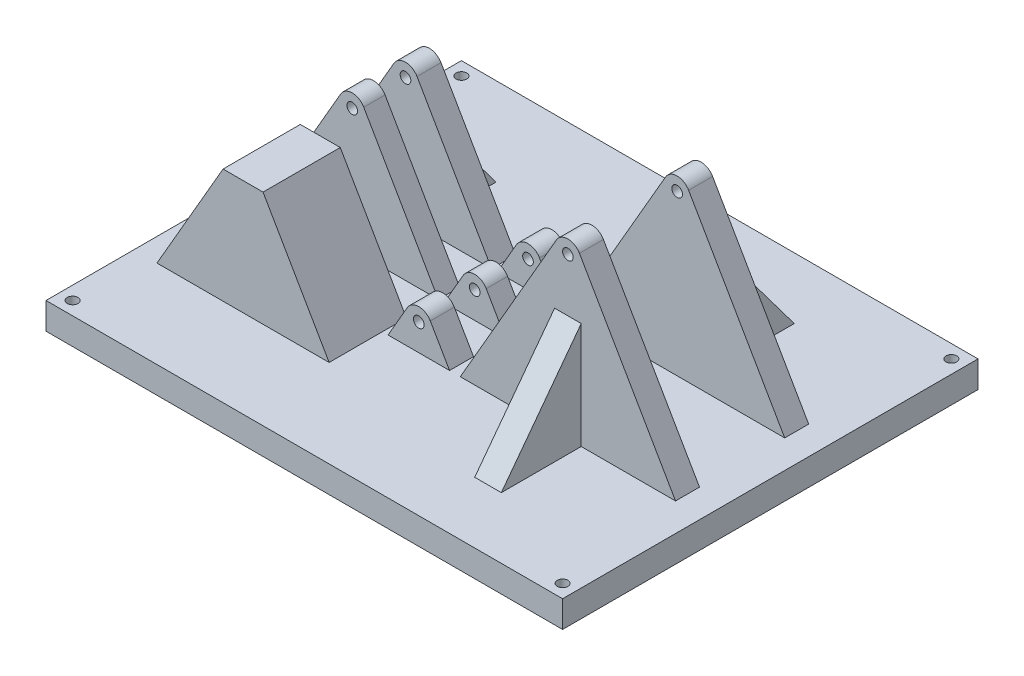
SolidWorks part; units mm, degrees
ref_plane "Front Plane" through (0, 0, 0) normal (0, 0, 1) x (1, 0, 0)
ref_plane "Top Plane" through (0, 0, 0) normal (0, 1, 0) x (1, 0, 0)
ref_plane "Right Plane" through (0, 0, 0) normal (1, 0, 0) x (0, 0, -1)
sketch "Sketch2" plane through (0, 0, 0) normal (0, 0, 1) x (1, 0, 0)
  line L0 (41.6699, 12.5) -> (5.5855, -50)
  line L1 (-97, -50) -> (97, -50)
  line L2 (-97, -50) -> (-97, 50)
  line L3 (-97, 50) -> (97, 50)
  line L4 (97, -50) -> (97, 50)
  line L5 (-97, -50) -> (97, 50) construction
  line L6 (-97, 50) -> (97, -50) construction
  line L7 (-88.3316, -50) -> (-60.3301, -1.5)
  line L8 (-23.6684, -50) -> (-51.6699, -1.5)
  line L9 (-14.3301, -37.5) -> (-21.547, -50)
  line L10 (-5.6699, -37.5) -> (1.547, -50)
  line L11 (50.3301, 12.5) -> (86.4145, -50)
  circle A0 centre (-10, -40) radius 2
  circle A1 centre (-56, -4) radius 2
  circle A2 centre (46, 10) radius 2
  arc A3 (-51.6699, -1.5) -> (-60.3301, -1.5) centre (-56, -4) ccw
  arc A5 (-5.6699, -37.5) -> (-14.3301, -37.5) centre (-10, -40) ccw
  arc A6 (50.3301, 12.5) -> (41.6699, 12.5) centre (46, 10) ccw
  point P0 (0, 0)
extrude "Boss-Extrude2" add sketch "Sketch2" along normal mid plane 10 contours L11 A6 L0 L1 A2 | L10 A5 L9 L1 A0 | L8 A3 L7 L1 A1 region at (46, -27.0942, 0) region at (-10, -44.3629, 0) region at (-56, -31.8498, 0)
sketch "Sketch3" plane through (0, -50, 0) normal (0, -1, 0) x (-1, 0, 0)
  line L1 (97, 78) -> (-97, 78)
  line L2 (97, 78) -> (97, -78)
  line L3 (97, -78) -> (-97, -78)
  line L4 (-97, 78) -> (-97, -78)
  line L5 (97, 78) -> (-97, -78) construction
  line L6 (97, -78) -> (-97, 78) construction
  point P0 (0, 0)
extrude "Boss-Extrude3" add sketch "Sketch3" along normal blind 10
ref_plane "Plane1" through (0, 0, 15) normal (0, 0, 1) x (1, 0, 0)
sketch "Sketch5" plane through (0, 0, 15) normal (0, 0, 1) x (1, 0, 0)
  line L0 (41.6699, 12.5) -> (5.5855, -50)
  line L1 (-97, -50) -> (97, -50)
  line L2 (-97, -50) -> (-97, 50)
  line L3 (-97, 50) -> (97, 50)
  line L4 (97, -50) -> (97, 50)
  line L5 (-97, -50) -> (97, 50) construction
  line L6 (-97, 50) -> (97, -50) construction
  line L7 (-88.3316, -50) -> (-60.3301, -1.5)
  line L8 (-23.6684, -50) -> (-51.6699, -1.5)
  line L9 (-14.3301, -37.5) -> (-21.547, -50)
  line L10 (-5.6699, -37.5) -> (1.547, -50)
  line L11 (50.3301, 12.5) -> (86.4145, -50)
  circle A0 centre (-10, -40) radius 2
  circle A1 centre (-56, -4) radius 2
  circle A2 centre (46, 10) radius 2
  arc A3 (-51.6699, -1.5) -> (-60.3301, -1.5) centre (-56, -4) ccw
  arc A4 (-5.6699, -37.5) -> (-14.3301, -37.5) centre (-10, -40) ccw
  arc A5 (50.3301, 12.5) -> (41.6699, 12.5) centre (46, 10) ccw
  point P0 (0, 0)
extrude "Boss-Extrude4" add sketch "Sketch5" along normal blind 10 contours L8 A3 L7 L1 A1 | L10 A4 L9 L1 A0 | L11 A5 L0 L1 A2 region at (46, -27.0942, 15) region at (-10, -44.3629, 15) region at (-56, -31.8498, 15)
mirror "Mirror1" about plane through (0, 0, 0) normal (0, 0, 1) of "Boss-Extrude4"
sketch "Sketch6" plane through (0, -50, 0) normal (0, 1, 0) x (1, 0, 0)
  line L1 (5.5855, 5) -> (86.4145, 5)
  line L2 (5.5855, 5) -> (5.5855, -5)
  line L3 (5.5855, -5) -> (86.4145, -5)
  line L4 (86.4145, 5) -> (86.4145, -5)
extrude "Cut-Extrude1" cut sketch "Sketch6" along normal blind 142
sketch "Sketch7" plane through (0, -50, 0) normal (0, 1, 0) x (1, 0, 0)
  line L5 (-97, -78) -> (97, 78) construction
  line L6 (-97, 78) -> (97, -78) construction
  circle A5 centre (-92, -73) radius 2
  circle A6 centre (-92, 73) radius 2
  circle A7 centre (92, 73) radius 2
  circle A8 centre (92, -73) radius 2
  point P0 (0, 0)
extrude "Cut-Extrude2" cut sketch "Sketch7" against normal blind 142
sketch "Sketch8" plane through (0, 0, 25) normal (0, 0, 1) x (1, 0, 0)
  line L2 (-71, -7) -> (-41, -7)
  line L3 (-71, -7) -> (-71, -1)
  line L5 (-41, -7) -> (-41, -1)
  line L9 (-71, -1) -> (-71, 3.0286)
  line L10 (-71, 3.0286) -> (-41, 3.0286)
  line L11 (-41, -1) -> (-41, 3.0286)
extrude "Cut-Extrude4" cut sketch "Sketch8" against normal blind 10
sketch "Sketch9" plane through (0, 0, 25) normal (0, 0, 1) x (1, 0, 0)
  line L0 (-88.3316, -50) -> (-23.6684, -50)
  line L1 (-23.6684, -50) -> (-48.4944, -7)
  line L2 (-48.4944, -7) -> (-63.5056, -7)
  line L3 (-63.5056, -7) -> (-88.3316, -50)
extrude "Boss-Extrude5" add sketch "Sketch9" along normal blind 20
sketch "Sketch10" plane through (0, 0, 5) normal (0, 0, 1) x (1, 0, 0)
  line L0 (-60.3301, -1.5) -> (-88.3316, -50)
  line L1 (-88.3316, -50) -> (-23.6684, -50)
  line L2 (-23.6684, -50) -> (-51.6699, -1.5)
  line L3 (-21.547, -50) -> (-14.3301, -37.5)
  line L5 (-5.6699, -37.5) -> (1.547, -50)
  line L6 (1.547, -50) -> (-21.547, -50)
  arc A0 (-51.6699, -1.5) -> (-60.3301, -1.5) centre (-56, -4) ccw
  circle A1 centre (-56, -4) radius 2
  arc A2 (-5.6699, -37.5) -> (-14.3301, -37.5) centre (-10, -40) ccw
extrude "Cut-Extrude5" cut sketch "Sketch10" against normal blind 1
mirror "Mirror2" about plane through (0, 0, 0) normal (0, 0, 1) of "Cut-Extrude5"
sketch "Sketch11" plane through (0, 0, -15) normal (0, 0, 1) x (1, 0, 0)
  line L0 (-88.3316, -50) -> (-23.6684, -50)
  line L1 (-23.6684, -50) -> (-51.6699, -1.5)
  line L2 (-21.547, -50) -> (1.547, -50)
  line L3 (-88.3316, -50) -> (-60.3301, -1.5)
  line L4 (1.547, -50) -> (-5.6699, -37.5)
  line L6 (-14.3301, -37.5) -> (-21.547, -50)
  line L7 (5.5855, -50) -> (41.6699, 12.5)
  line L9 (50.3301, 12.5) -> (86.4145, -50)
  line L10 (86.4145, -50) -> (5.5855, -50)
  arc A0 (-51.6699, -1.5) -> (-60.3301, -1.5) centre (-56, -4) ccw
  arc A1 (-5.6699, -37.5) -> (-14.3301, -37.5) centre (-10, -40) ccw
  arc A2 (50.3301, 12.5) -> (41.6699, 12.5) centre (46, 10) ccw
extrude "Cut-Extrude6" cut sketch "Sketch11" against normal blind 1
mirror "Mirror3" about plane through (0, 0, 0) normal (0, 0, 1) of "Cut-Extrude6"
ref_axis "Axis1" through (46, 10, 25) along (0, 0, -1)
ref_plane "Plane2" through (46, 0, 0) normal (1, 0, 0) x (0, 0, -1)
sketch "Sketch12" plane through (46, 0, 0) normal (1, 0, 0) x (0, 0, -1)
  line L0 (-55, -50) -> (-25, -10)
  line L2 (-55, -50) -> (-25, -50)
  line L3 (-25, -50) -> (-25, -10)
extrude "Boss-Extrude6" add sketch "Sketch12" along normal mid plane 10
mirror "Mirror4" about plane through (0, 0, 0) normal (0, 0, 1) of "Boss-Extrude6"
ref_axis "Axis2" through (-56, -4, -25) along (0, 0, 1)
ref_plane "Plane3" through (-56, 0, 0) normal (-1, 0, 0) x (0, 0, 1)
sketch "Sketch13" plane through (-56, 0, 0) normal (-1, 0, 0) x (0, 0, 1)
  line L1 (-45, -50) -> (-25, -23.3333)
  line L2 (-25, -50) -> (-25, -1.5) construction
  line L3 (-45, -50) -> (-25, -50)
  line L4 (-25, -50) -> (-25, -23.3333)
extrude "Boss-Extrude7" add sketch "Sketch13" along normal mid plane 10
